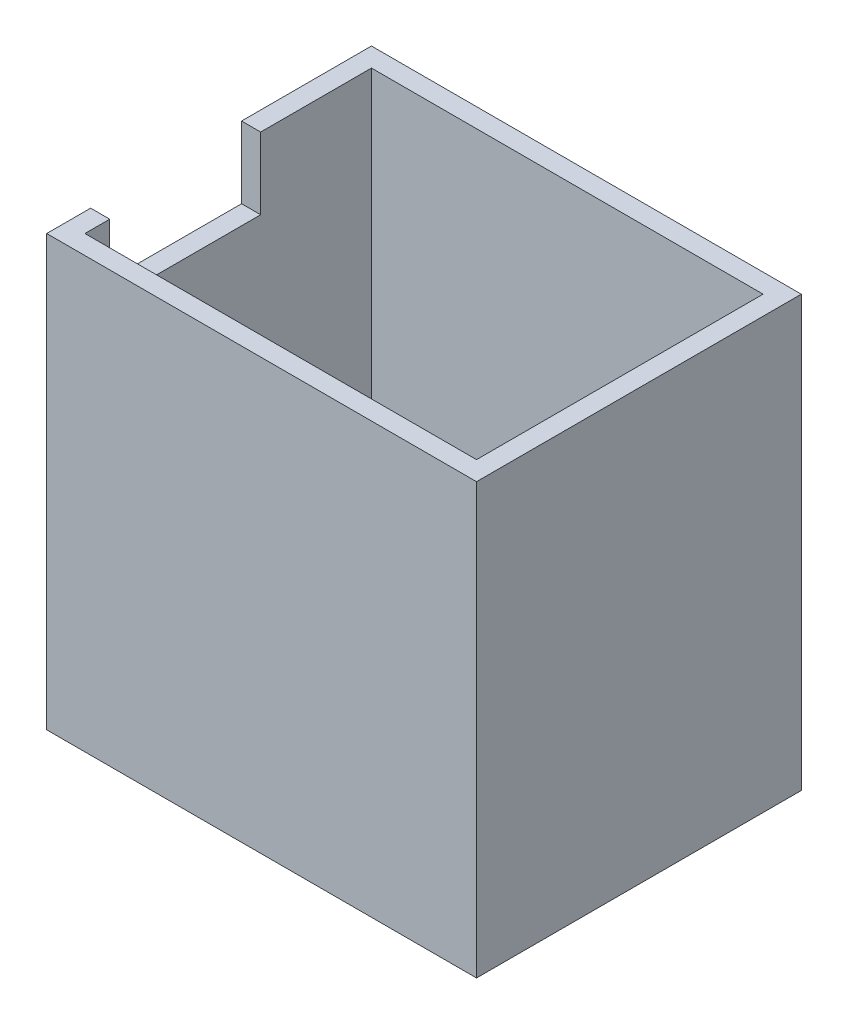
SolidWorks part; units mm, degrees
ref_plane "Front Plane" through (0, 0, 0) normal (0, 0, 1) x (1, 0, 0)
ref_plane "Top Plane" through (0, 0, 0) normal (0, 1, 0) x (1, 0, 0)
ref_plane "Right Plane" through (0, 0, 0) normal (1, 0, 0) x (0, 0, -1)
sketch "Sketch1" plane through (0, 0, 0) normal (0, 1, 0) x (1, 0, 0)
  line L1 (-28.575, -21.59) -> (28.575, -21.59)
  line L2 (-28.575, -21.59) -> (-28.575, 21.59)
  line L3 (-28.575, 21.59) -> (28.575, 21.59)
  line L4 (28.575, -21.59) -> (28.575, 21.59)
  line L5 (-28.575, -21.59) -> (28.575, 21.59) construction
  line L6 (-28.575, 21.59) -> (28.575, -21.59) construction
  point P0 (0, 0)
  dimension "D1" = 57.15
  dimension "D2" = 43.18
extrude "Base" add sketch "Sketch1" along normal blind 57.15
sketch "Sketch2" plane through (0, 57.15, 0) normal (0, 1, 0) x (1, 0, 0)
  line L1 (26.035, -19.05) -> (-26.035, -19.05)
  line L2 (26.035, -19.05) -> (26.035, 19.05)
  line L3 (26.035, 19.05) -> (-26.035, 19.05)
  line L4 (-26.035, -19.05) -> (-26.035, 19.05)
  line L5 (26.035, -19.05) -> (-26.035, 19.05) construction
  line L6 (26.035, 19.05) -> (-26.035, -19.05) construction
  point P0 (0, 0)
  dimension "D1" = 38.1
  dimension "D2" = 52.07
extrude "Pocket" cut sketch "Sketch2" against normal blind 47.9552
sketch "Sketch3" plane through (0, 0, 0) normal (0, -1, 0) x (-1, 0, 0)
  line L0 (28.575, 0) -> (-28.575, 0) construction
  line L1 (7.493, -7.747) -> (-10.795, -7.747)
  line L2 (7.493, -7.747) -> (7.493, 7.747)
  line L3 (7.493, 7.747) -> (-10.795, 7.747)
  line L4 (-10.795, -7.747) -> (-10.795, 7.747)
  line L5 (7.493, -7.747) -> (-10.795, 7.747) construction
  line L6 (7.493, 7.747) -> (-10.795, -7.747) construction
  line L7 (28.575, 21.59) -> (28.575, -21.59) construction
  line L8 (-28.575, -21.59) -> (-28.575, 21.59) construction
  point P0 (-1.651, 0)
  dimension "D1" = 15.494
  dimension "D2" = 18.288
  dimension "D3" = 21.082
extrude "LinActHole" cut sketch "Sketch3" against normal through all
sketch "Sketch4" plane through (-28.575, 0, 0) normal (-1, 0, 0) x (0, 0, 1)
  line L0 (-21.59, 57.15) -> (21.59, 57.15) construction
  line L1 (15.748, 57.15) -> (-4.318, 57.15)
  line L2 (15.748, 57.15) -> (15.748, 47.625)
  line L3 (15.748, 47.625) -> (-4.318, 47.625)
  line L4 (-4.318, 57.15) -> (-4.318, 47.625)
  line L5 (21.59, 57.15) -> (21.59, 0) construction
  line L6 (-21.59, 57.15) -> (-21.59, 0) construction
  dimension "D1" = 5.842
  dimension "D2" = 17.272
  dimension "D3" = 9.525
extrude "RollMotorHole" cut sketch "Sketch4" against normal up to next
sketch "Sketch5" plane through (0, 0, 0) normal (0, -1, 0) x (1, 0, 0)
  line L1 (17.6249, -13.716) -> (24.2289, -13.716)
  line L2 (15.0849, -11.176) -> (15.0849, 11.176)
  line L3 (17.6249, 13.716) -> (24.2289, 13.716)
  line L4 (24.2289, -13.716) -> (24.2289, 13.716)
  line L5 (15.0849, -13.716) -> (24.2289, 13.716) construction
  line L6 (15.0849, 13.716) -> (24.2289, -13.716) construction
  arc A0 (15.0849, -11.176) -> (17.6249, -13.716) centre (17.6249, -11.176) ccw
  arc A1 (15.0849, 11.176) -> (17.6249, 13.716) centre (17.6249, 11.176) cw
  point P0 (19.6569, 0)
  dimension "D3" = 2.54
  dimension "D1" = 27.432
  dimension "D2" = 9.144
extrude "DviHole" cut sketch "Sketch5" against normal up to next
hole_wizard "CBORE for #4 Socket Head Cap Screw1" positions "Sketch7" profile "Sketch6" counterbore size "#4" standard "ANSI Inch" end condition through all
sketch "Sketch7" plane through (0, 0, 0) normal (0, -1, 0) x (-1, 0, 0)
  line L0 (-19.6569, 21.59) -> (-19.6569, -21.59) construction
  line L1 (-28.575, 21.59) -> (28.575, 21.59) construction
  line L2 (28.575, -21.59) -> (-28.575, -21.59) construction
  line L3 (-24.2289, 13.716) -> (-24.2289, -13.716) construction
  line L4 (-24.2289, 0) -> (-15.0849, 0) construction
  line L5 (-15.0849, -11.176) -> (-15.0849, 11.176) construction
  point P0 (-19.6569, 16.256)
  point P2 (-19.6569, -16.256)
  dimension "D1" = 4.572
  dimension "D2" = 32.512
sketch "Sketch6" plane through (19.6569, 0, -16.256) normal (1, 0, 0) x (0, 0, -1)
  line L0 (0, 0) -> (0, 57.15)
  line L1 (0, 57.15) -> (1.6319, 57.15)
  line L3 (1.6319, 57.15) -> (1.632, 2.8448)
  line L4 (1.632, 2.8448) -> (3.175, 2.8448)
  line L5 (3.175, 2.8448) -> (3.175, 0)
  line L7 (3.175, 0) -> (0, 0)
  line L11 (0, -6.35) -> (0, 107.95) construction
  dimension "Thru Hole Dia." = 3.2639
  dimension "Thru Hole Depth" = 57.15
  dimension "C'Bore Dia." = 6.35
  dimension "C'Bore Depth" = 2.8448
hole_wizard "CBORE for #8 Socket Head Cap Screw1" positions "Sketch9" profile "Sketch8" counterbore size "#8" standard "ANSI Inch" end condition through all
sketch "Sketch9" plane through (0, 0, 0) normal (0, -1, 0) x (-1, 0, 0)
  line L0 (3.175, -21.59) -> (3.175, 21.59) construction
  line L1 (28.575, -21.59) -> (-28.575, -21.59) construction
  line L2 (-28.575, 21.59) -> (28.575, 21.59) construction
  line L3 (28.575, 0) -> (-28.575, 0) construction
  line L4 (28.575, 21.59) -> (28.575, -21.59) construction
  line L5 (-28.575, -21.59) -> (-28.575, 21.59) construction
  point P0 (3.175, 14.605)
  point P2 (3.175, -14.605)
  dimension "D1" = 31.75
  dimension "D2" = 29.21
sketch "Sketch8" plane through (-3.175, 0, -14.605) normal (1, 0, 0) x (0, 0, -1)
  line L0 (0, 0) -> (0, 57.15)
  line L1 (0, 57.15) -> (2.2479, 57.15)
  line L3 (2.2479, 57.15) -> (2.2479, 4.1656)
  line L4 (2.2479, 4.1656) -> (3.9688, 4.1656)
  line L5 (3.9688, 4.1656) -> (3.9688, 0)
  line L7 (3.9688, 0) -> (0, 0)
  line L11 (0, -6.35) -> (0, 107.95) construction
  dimension "Thru Hole Dia." = 4.4958
  dimension "Thru Hole Depth" = 57.15
  dimension "C'Bore Dia." = 7.9375
  dimension "C'Bore Depth" = 4.1656
fillet "Fillet1" radius 0.254 4 edges at (21.5619, 1.4224, -13.716) (17.7519, 1.4224, -13.716) (21.5619, 1.4224, 13.716) (17.7519, 1.4224, 13.716)
